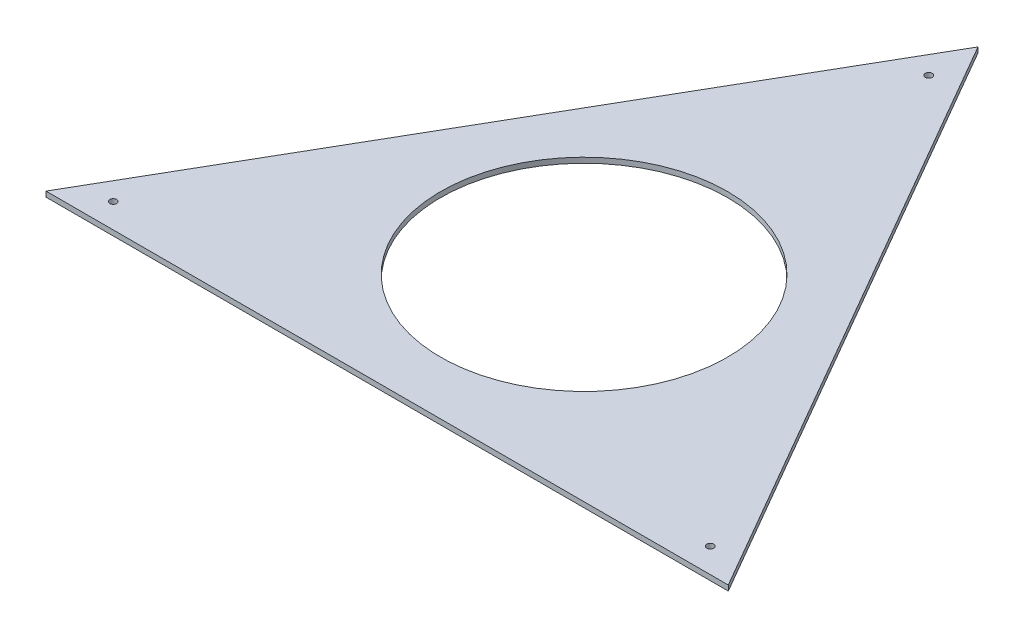
SolidWorks part; units mm, degrees
ref_plane "Front Plane" through (0, 0, 0) normal (0, 0, 1) x (1, 0, 0)
ref_plane "Top Plane" through (0, 0, 0) normal (0, 1, 0) x (1, 0, 0)
ref_plane "Right Plane" through (0, 0, 0) normal (1, 0, 0) x (0, 0, -1)
sketch "Sketch1" plane through (0, 0, 0) normal (0, 1, 0) x (1, 0, 0)
  line L1 (0, 355.6) -> (-307.9586, -177.8)
  line L2 (-307.9586, -177.8) -> (307.9586, -177.8)
  line L3 (307.9586, -177.8) -> (0, 355.6)
  circle A0 centre (0, 0) radius 177.8 construction
  dimension "D1" = 355.6
extrude "Boss-Extrude1" add sketch "Sketch1" along normal blind 4.7625 contours L1 L2 L3
sketch "Sketch5" plane through (0, 0, 0) normal (0, 1, 0) x (1, 0, 0)
  circle A0 centre (0, 0) radius 129.54
  dimension "D1" = 259.08
extrude "Cut-Extrude3" cut sketch "Sketch5" against normal blind 4.7625 and the other way blind 4.7625
sketch "Sketch6" plane through (0, 0, 0) normal (0, 1, 0) x (1, 0, 0)
  line L2 (0, 355.6) -> (-307.9586, -177.8) construction
  line L8 (-307.9586, -177.8) -> (307.9586, -177.8) construction
  line L13 (307.9586, -177.8) -> (0, 355.6) construction
  circle A0 centre (-269.4638, -155.575) radius 3.175
  circle A1 centre (0, 311.15) radius 3.175
  dimension "D1" = 19.05
  dimension "D2" = 19.05
  dimension "D3" = 6.35
  dimension "D4" = 19.05
  dimension "D5" = 19.05
  dimension "D6" = 6.35
extrude "Cut-Extrude5" cut sketch "Sketch6" along normal blind 4.7625
mirror "Mirror1" about plane through (0, 0, 0) normal (1, 0, 0) of "Cut-Extrude5"
